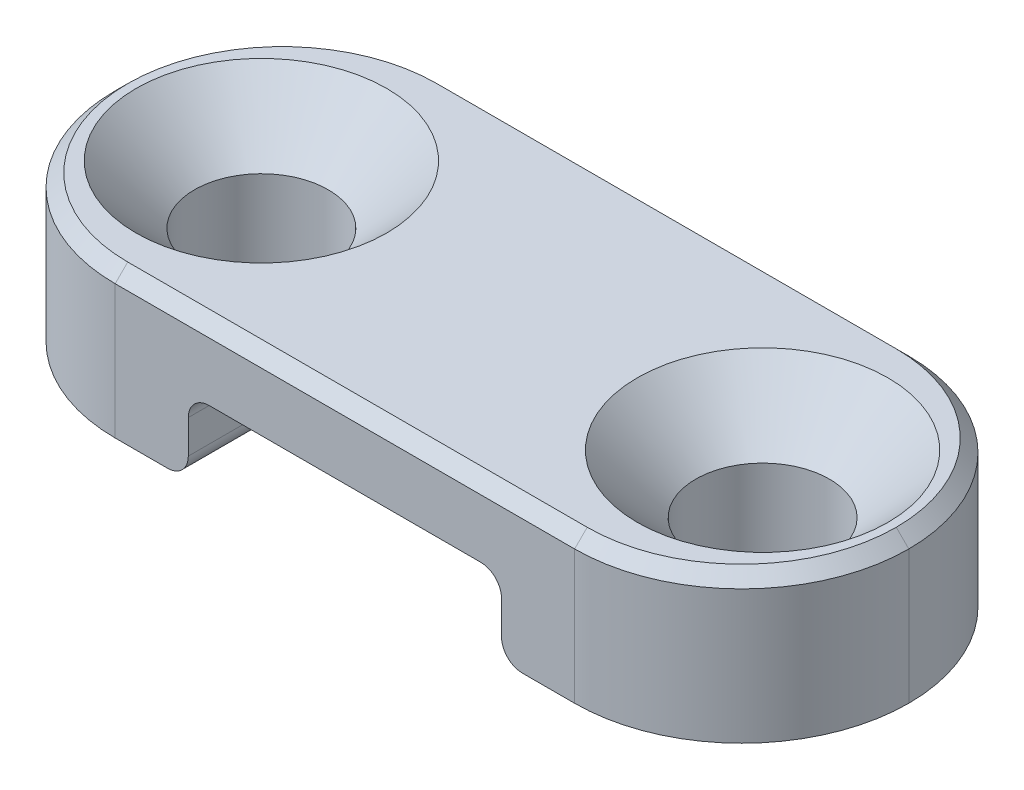
SolidWorks part; units mm, degrees
material "ABS"
ref_plane "前视基准面" through (0, 0, 0) normal (0, 0, 1) x (1, 0, 0)
ref_plane "上视基准面" through (0, 0, 0) normal (0, 1, 0) x (1, 0, 0)
ref_plane "右视基准面" through (0, 0, 0) normal (1, 0, 0) x (0, 0, -1)
other "Configuration Table"
sketch "草图1" plane through (0, 0, 0) normal (0, 1, 0) x (1, 0, 0)
  line L1 (-9.5, -4) -> (9.5, -4)
  line L2 (-9.5, -4) -> (-9.5, 4)
  line L3 (-9.5, 4) -> (9.5, 4)
  line L4 (9.5, -4) -> (9.5, 4)
  line L5 (-9.5, -4) -> (9.5, 4) construction
  line L6 (-9.5, 4) -> (9.5, -4) construction
  point P0 (0, 0)
  dimension "D1" = 19
  dimension "D2" = 8
extrude "凸台-拉伸1" add sketch "草图1" along normal mid plane 3.5
sketch "草图2" plane through (0, 0, 4) normal (0, 0, 1) x (1, 0, 0)
  line L0 (-9.5, -1.75) -> (9.5, -1.75) construction
  line L3 (-3.75, -1.75) -> (3.75, -1.75)
  line L4 (-3.75, -1.75) -> (-3.75, 0.05)
  line L5 (-3.75, 0.05) -> (3.75, 0.05)
  line L6 (3.75, -1.75) -> (3.75, 0.05)
  line L7 (-3.75, -1.75) -> (3.75, 0.05) construction
  line L8 (-3.75, 0.05) -> (3.75, -1.75) construction
  point P0 (0, -0.85)
  dimension "D1" = 1.8
  dimension "D2" = 7.5
extrude "切除-拉伸1" cut sketch "草图2" against normal up to next
sketch "草图3" plane through (0, 1.75, 0) normal (0, 1, 0) x (1, 0, 0)
  line L0 (0, 0) -> (-9.5, 0) construction
  line L1 (-9.5, 4) -> (-9.5, -4) construction
  line L2 (0, -1.925) -> (0, 1.925) construction
  circle A0 centre (-6, 0) radius 1.5 construction
  circle A1 centre (6, 0) radius 1.5 construction
  point P6 (-6, 0)
  point P9 (6, 0)
  point P14 (-6, 0)
  point P18 (6, 0)
  dimension "D2" = 3
  dimension "D1" = 6
hole_wizard "M3 十字槽半沉头木螺钉的锥形沉头孔1" positions "草图3" profile "草图6" countersink size "M3" standard "GB" end condition through all
sketch "草图6" plane through (6, 1.75, 0) normal (1, 0, 0) x (0, 0, 1)
  line L0 (0, 0) -> (0, 3.5)
  line L1 (0, 3.5) -> (1.6, 3.5)
  line L2 (1.6, 3.5) -> (1.6, 1.4)
  line L3 (1.6, 1.4) -> (3, 0)
  line L5 (3, 0) -> (0, 0)
  line L6 (-1.6, 1.4) -> (-3, 0) construction
  line L11 (0, -6.35) -> (0, 107.95) construction
  dimension "通孔孔直径" = 3.2
  dimension "通孔孔深度" = 3.5
  dimension "近端锥形沉头孔直径" = 6
  dimension "近端锥形沉头孔角度" = 90
fillet "圆角2" radius 4 4 edges at (9.5, 0, 4) (-9.5, 0, -4) (9.5, 0, -4) (-9.5, 0, 4)
fillet "圆角3" radius 0.5 4 edges at (-3.75, -1.75, 0) (3.75, -1.75, 0) (3.75, 0.05, 0) (-3.75, 0.05, 0)
chamfer "倒角1" distance 0.3 angle 45 6 edges at (-8.3284, 1.75, -2.8284) (-8.3284, 1.75, 2.8284) (0, 1.75, -4) (0, 1.75, 4) (8.3284, 1.75, -2.8284) (8.3284, 1.75, 2.8284)
